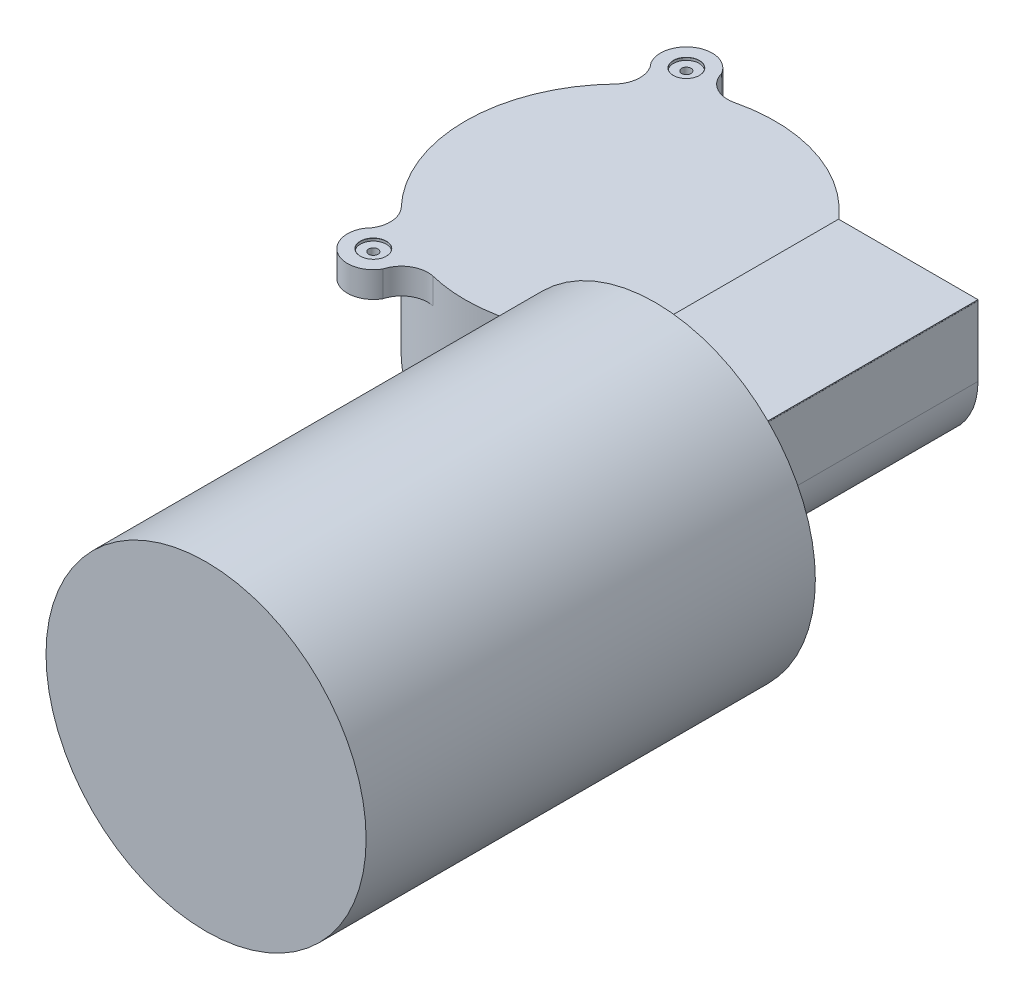
SolidWorks part; units mm, degrees
ref_plane "Front Plane" through (0, 0, 0) normal (0, 0, 1) x (1, 0, 0)
ref_plane "Top Plane" through (0, 0, 0) normal (0, 1, 0) x (1, 0, 0)
ref_plane "Right Plane" through (0, 0, 0) normal (1, 0, 0) x (0, 0, -1)
sketch "Sketch1" plane through (0, 0, 0) normal (0, 0, 1) x (1, 0, 0)
  circle A0 centre (0, 0) radius 31
  dimension "D1" = 62
extrude "Boss-Extrude1" add sketch "Sketch1" along normal blind 87 contours A0
sketch "Sketch2" plane through (0, 0, 0) normal (0, 0, 1) x (1, 0, 0)
  line L0 (0, 0) -> (0, 310) construction
  line L1 (-13.5, 13.5) -> (13.5, 13.5)
  line L2 (-13.5, 27) -> (13.5, 27)
  line L3 (-13.5, 27) -> (-13.5, 0)
  line L4 (-13.5, 0) -> (13.5, 0)
  line L5 (13.5, 27) -> (13.5, 0)
  line L6 (-13.5, 27) -> (13.5, 0) construction
  line L7 (-13.5, 0) -> (13.5, 27) construction
  circle A0 centre (0, 0) radius 13.5
  point P3 (0, 13.5)
  dimension "D1" = 27
  dimension "D2" = 27
extrude "Boss-Extrude2" add sketch "Sketch2" against normal blind 49 contours A0 L1 L3 | A0 L5 L1 | L4 A0 | L4 A0 region at (-10.4845, 10.4845, 0) region at (10.4845, 10.4845, 0) region at (0, 5.7296, 0) region at (0, -5.7296, 0)
sketch "Sketch4" plane through (0, 13.5, 0) normal (0, 1, 0) x (1, 0, 0)
  line L0 (-13.5, 24.5) -> (13.5, 24.5) construction
  line L1 (-13.5, 49) -> (-13.5, 0) construction
  line L2 (13.5, 49) -> (13.5, 0) construction
  line L3 (-36.3191, 29.5247) -> (-51.3191, 55.5054) construction
  line L4 (-51.3191, 55.5054) -> (-60.0048, 70.5495) construction
  line L5 (-36.3191, 29.5247) -> (-51.3191, 3.5439) construction
  line L6 (-51.3191, 3.5439) -> (-57.1339, -6.5276) construction
  line L7 (-51.3191, 55.5054) -> (-36.3191, 64.1657) construction
  line L8 (-53.8191, 59.8356) -> (-45.1589, 64.8356) construction
  line L9 (-36.3191, 64.1657) -> (-62.9795, 48.7733) construction
  line L10 (-53.8191, 59.8356) -> (-62.5189, 54.8128) construction
  line L11 (-51.3191, 3.5439) -> (-41.8627, -1.9157) construction
  line L12 (-41.8627, -1.9157) -> (-67.479, 12.8738) construction
  line L13 (-53.8191, -0.7862) -> (-70.4619, 8.8225) construction
  line L14 (-53.8191, -0.7862) -> (-40.5556, -8.4439) construction
  line L15 (-13.5, 49) -> (-13.5, 10.0494)
  circle A0 centre (-36.3191, 29.5247) radius 30
  circle A1 centre (-53.8191, 59.8356) radius 5
  circle A2 centre (-53.8191, -0.7862) radius 5
  arc A3 (-58.169, 57.3242) -> (-58.169, 50.0815) centre (-61.7903, 53.7028) cw
  arc A4 (-49.489, 62.3356) -> (-43.1969, 58.7256) centre (-44.538, 63.6766) ccw
  arc A5 (-58.1492, 1.7138) -> (-58.169, 8.9679) centre (-61.7861, 5.331) ccw
  arc A6 (-49.489, -3.2862) -> (-43.1969, 0.3237) centre (-44.538, -4.6273) cw
  point P6 (-51.3191, 55.5054)
  point P7 (-51.3191, 3.5439)
  point P12 (-6.3191, 29.5247)
  point P23 (-49.489, 62.3356)
  point P29 (-43.1969, 58.7256)
  point P33 (-58.1492, 1.7138)
  point P38 (-49.489, -3.2862)
  point P39 (-43.1969, 0.3237)
  point P40 (-58.169, 8.9679)
  dimension "D1" = 60
  dimension "D4" = 8.7373
  dimension "D2" = 120
  dimension "D3" = 120
  dimension "D5" = 8.7373
  dimension "D6" = 8.7373
  dimension "D7" = 8.7373
extrude "Boss-Extrude35" add sketch "Sketch4" against normal blind 24.5 separate body contours A0
sketch "Sketch12" plane through (0, -11, 0) normal (0, -1, 0) x (1, 0, 0)
  line L0 (-36.3191, -29.5247) -> (-20.787, -29.5247) construction
  line L1 (-36.3191, 0.4753) -> (-36.3191, -59.5247) construction
  circle A0 centre (-36.3191, -29.5247) radius 9.525
  circle A1 centre (-41.0816, -21.2758) radius 1.5875
  circle A2 centre (-26.7941, -29.5247) radius 1.5875
  circle A3 centre (-41.0816, -37.7736) radius 1.5875
  circle A4 centre (-41.0816, -21.2758) radius 0.7937
  circle A5 centre (-26.7941, -29.5247) radius 0.7937
  circle A6 centre (-41.0816, -37.7736) radius 0.7937
  circle A7 centre (-36.3191, -29.5247) radius 30 construction
  point P0 (-36.3191, -29.5247)
  point P4 (-26.7941, -29.5247)
  point P6 (-41.0816, -21.2758)
  point P7 (-41.0816, -37.7736)
  dimension "D1" = 19.05
  dimension "D4" = 3.175
  dimension "D5" = 1.5875
  dimension "D2" = 120
  dimension "D3" = 120
extrude "Boss-Extrude36" add sketch "Sketch12" along normal blind 17.5 contours A5 A0 A2 | A5 A0 A2 | A6 A0 A3 | A6 A0 A3 | A4 A0 A1 | A4 A0 A1 region at (-27.6121, -11, -29.5247) region at (-26.8327, -11, -28.3316) region at (-40.6726, -11, -21.9842) region at (-40.0303, -11, -20.7099) region at (-41.8558, -11, -39.1145) region at (-40.6726, -11, -37.0652)
sketch "Sketch14" plane through (0, -11, 0) normal (0, -1, 0) x (1, 0, 0)
  line L0 (-36.3191, 0.4753) -> (-36.3191, -59.5247) construction
  circle A0 centre (-36.3191, -29.5247) radius 5
  circle A1 centre (-36.3191, -29.5247) radius 30 construction
  dimension "D1" = 10
extrude "Boss-Extrude37" add sketch "Sketch14" along normal blind 17.5
sketch "Sketch16" plane through (0, -28.5, 0) normal (0, -1, 0) x (1, 0, 0)
  line L0 (-32.3191, -29.5247) -> (-40.3191, -29.5247) construction
  line L1 (-39.8191, -31.4612) -> (-39.8191, -27.5882)
  line L2 (-32.8191, -31.4612) -> (-32.8191, -27.5882)
  line L3 (-36.3191, -24.5247) -> (-36.3191, -34.5247) construction
  circle A0 centre (-36.3191, -29.5247) radius 4
  circle A1 centre (-36.3191, -29.5247) radius 5 construction
  circle A2 centre (-36.3191, -29.5247) radius 5 construction
  point P8 (-39.8191, -29.5247)
  point P11 (-32.8191, -29.5247)
  dimension "D1" = 8
  dimension "D2" = 3.873
extrude "Boss-Extrude38" add sketch "Sketch16" along normal blind 3.175 contours L2 A0 L1 region at (-36.3191, -28.5, -29.5247)
sketch "Sketch17" plane through (0, -31.675, 0) normal (0, -1, 0) x (1, 0, 0)
  line L0 (-36.3191, -25.5247) -> (-36.3191, -33.5247) construction
  circle A0 centre (-36.3191, -29.5247) radius 3
  arc A1 (-32.8191, -27.5882) -> (-39.8191, -27.5882) centre (-36.3191, -29.5247) ccw construction
  arc A2 (-39.8191, -31.4612) -> (-32.8191, -31.4612) centre (-36.3191, -29.5247) ccw construction
extrude "Boss-Extrude39" add sketch "Sketch17" along normal blind 3.188
extrude "Boss-Extrude40" add sketch "Sketch4<14>" against normal blind 5 contours A4 A1 A3 | A1 A3 A0 | A4 A1 A0 | A2 A6 A5 | A2 A6 A0 | A5 A2 A0 region at (-47.8244, 13.5, -58.2882) region at (-47.8244, 13.5, -0.7612) region at (-55.4881, 13.5, -53.873) region at (-53.821, 13.5, -59.8357) region at (-55.4764, 13.5, -5.179) region at (-53.8197, 13.5, 0.7873)
sketch "Sketch4<14>" plane through (0, 13.5, 0) normal (0, 1, 0) x (1, 0, 0) same geometry as "Sketch4"
sketch "Sketch19" plane through (0, 13.5, 0) normal (0, 1, 0) x (1, 0, 0)
  arc A0 (-58.1027, 57.2567) -> (-49.489, 62.3356) centre (-53.8191, 59.8356) cw
  circle A1 centre (-53.8191, 59.8356) radius 3.175
  arc A2 (-58.1492, 1.7138) -> (-49.489, -3.2862) centre (-53.8191, -0.7862) ccw
  circle A3 centre (-53.8191, -0.7862) radius 3.175
  dimension "D1" = 6.35
hole_wizard "CBORE for M1.6 Hexagon head bolts-Full thread-grades AB1" positions "3DSketch1" profile "Sketch21" counterbore size "M1.6" standard "GB" end condition up to next
sketch3d "3DSketch1"
  point P0 (-53.8191, 13.5, -59.8356)
  point P3 (-53.8191, 13.5, 0.7862)
sketch "Sketch21" plane through (-53.8191, 13.5, -59.8356) normal (1, 0, 0) x (0, 0, 1)
  line L0 (0, 0) -> (0, 5.001)
  line L1 (0, 5.001) -> (0.9, 5.001)
  line L3 (0.9, 5.001) -> (0.9, 0.5)
  line L4 (2.5, 0.5) -> (0.9, 0.5)
  line L5 (2.5, 0.5) -> (2.5, 0.025)
  line L6 (2.5, 0.025) -> (2.525, 0)
  line L7 (2.525, 0) -> (0, 0)
  line L8 (-2.5, 0.025) -> (-2.525, 0) construction
  line L11 (0, -6.35) -> (0, 107.95) construction
  dimension "Thru Hole Dia." = 1.8
  dimension "Thru Hole Depth" = 5.001
  dimension "C'Bore Dia." = 5
  dimension "C'Bore Depth" = 0.5
  dimension "Near C'Sink Dia." = 5.05
  dimension "Near C'Sink Angle" = 90
sketch "Sketch23" plane through (0, 0, 0) normal (0, 0, -1) x (-1, 0, 0)
  line L1 (-13.5, 13.7138) -> (13.5, 13.7138)
  line L2 (-13.5, 13.7138) -> (-13.5, 13.5153)
  line L3 (-13.5, 13.5153) -> (13.5, 13.5153)
  line L4 (13.5, 13.7138) -> (13.5, 13.5153)
extrude "Boss-Extrude44" add sketch "Sketch23" along normal up to surface (49 mm away) up to face at (0, 3.375, -49)
